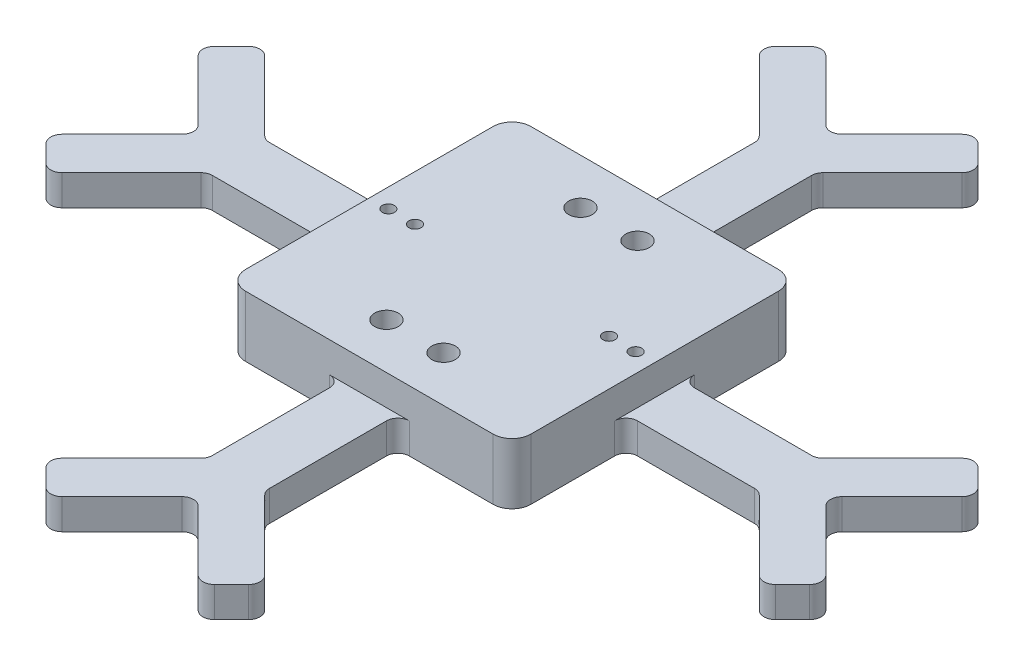
SolidWorks part; units mm, degrees
ref_plane "Front Plane" through (0, 0, 0) normal (0, 0, 1) x (1, 0, 0)
ref_plane "Top Plane" through (0, 0, 0) normal (0, 1, 0) x (1, 0, 0)
ref_plane "Right Plane" through (0, 0, 0) normal (1, 0, 0) x (0, 0, -1)
sketch "Sketch1" plane through (0, 0, 0) normal (0, 1, 0) x (1, 0, 0)
  line L0 (0, 37.5) -> (0, -37.5) construction
  line L1 (-37.5, 37.5) -> (37.5, 37.5)
  line L2 (-37.5, 37.5) -> (-37.5, -37.5)
  line L3 (-37.5, -37.5) -> (37.5, -37.5)
  line L4 (37.5, 37.5) -> (37.5, -37.5)
  line L5 (-37.5, 0) -> (37.5, 0) construction
  line L6 (-37.5, 0) -> (-20.5, 0) construction
  line L15 (-37.5, 5) -> (-20.5, 5) construction
  line L16 (-37.5, 5) -> (-37.5, -5) construction
  line L17 (-37.5, -5) -> (-20.5, -5) construction
  line L18 (-20.5, 5) -> (-20.5, -5) construction
  line L19 (-29, 5) -> (-29, -5) construction
  line L20 (29, 5) -> (29, -5) construction
  line L21 (37.5, 0) -> (20.5, 0) construction
  line L22 (20.5, 5) -> (20.5, -5) construction
  line L23 (37.5, -5) -> (20.5, -5) construction
  line L24 (37.5, 5) -> (37.5, -5) construction
  line L25 (37.5, 5) -> (20.5, 5) construction
  line L26 (-15, -25.5) -> (15, -25.5) construction
  line L27 (-15, -13.5) -> (15, -13.5) construction
  line L28 (-15, -13.5) -> (-15, -37.5) construction
  line L29 (-15, -37.5) -> (15, -37.5) construction
  line L30 (15, -13.5) -> (15, -37.5) construction
  line L31 (0, -13.5) -> (0, -37.5) construction
  line L32 (0, 13.5) -> (0, 37.5) construction
  line L33 (-15, 25.5) -> (15, 25.5) construction
  line L34 (15, 13.5) -> (15, 37.5) construction
  line L35 (-15, 37.5) -> (15, 37.5) construction
  line L36 (-15, 13.5) -> (-15, 37.5) construction
  line L37 (-15, 13.5) -> (15, 13.5) construction
  circle A2 centre (-32.5, 0) radius 1.6
  circle A3 centre (-25.5, 0) radius 1.6
  circle A4 centre (25.5, 0) radius 1.6
  circle A5 centre (32.5, 0) radius 1.6
  circle A6 centre (-7.5, -25.5) radius 3.1
  circle A7 centre (7.5, -25.5) radius 3.1
  circle A8 centre (7.5, 25.5) radius 3.1
  circle A9 centre (-7.5, 25.5) radius 3.1
  point P4 (0, 37.5)
  point P6 (-37.5, 0)
  point P19 (-29, 0)
  point P41 (29, 0)
  point P45 (0, 0)
  point P48 (0, -25.5)
  point P49 (0, 0)
  point P50 (0, 0)
  point P51 (0, 0)
  point P62 (0, 25.5)
  point P63 (45.5841, -44.9628)
  point P64 (37.328, -37.328)
  point P65 (51.459, -51.459)
  point P66 (-55.1118, 55.1118)
  dimension "D1" = 10
  dimension "D2" = 3.2
  dimension "D3" = 5
  dimension "D4" = 7
  dimension "D5" = 6.2
  dimension "D7" = 15
  dimension "D6" = 30
  dimension "D8" = 12
  dimension "D9" = 75
extrude "Boss-Extrude1" add sketch "Sketch1" along normal blind 8
sketch "Sketch3" plane through (0, 0, 0) normal (0, -1, 0) x (1, 0, 0)
  line L0 (-37.5, -37.5) -> (-37.5, 37.5) construction
  line L1 (37.5, -37.5) -> (-37.5, -37.5) construction
  line L2 (37.5, 37.5) -> (37.5, -37.5) construction
  line L3 (-37.5, 37.5) -> (37.5, 37.5) construction
  line L4 (-37.5, -37.5) -> (-37.5, 37.5)
  line L5 (37.5, -37.5) -> (-37.5, -37.5)
  line L6 (37.5, 37.5) -> (37.5, -37.5)
  line L7 (-37.5, 37.5) -> (37.5, 37.5)
  circle A0 centre (-7.5, -25.5) radius 3.1 construction
  circle A1 centre (7.5, -25.5) radius 3.1 construction
  circle A2 centre (32.5, 0) radius 1.6 construction
  circle A3 centre (25.5, 0) radius 1.6 construction
  circle A4 centre (7.5, 25.5) radius 3.1 construction
  circle A5 centre (-7.5, 25.5) radius 3.1 construction
  circle A6 centre (-25.5, 0) radius 1.6 construction
  circle A7 centre (-32.5, 0) radius 1.6 construction
  circle A8 centre (-7.5, -25.5) radius 3.1
  circle A9 centre (7.5, -25.5) radius 3.1
  circle A10 centre (32.5, 0) radius 1.6
  circle A11 centre (25.5, 0) radius 1.6
  circle A12 centre (7.5, 25.5) radius 3.1
  circle A13 centre (-7.5, 25.5) radius 3.1
  circle A14 centre (-25.5, 0) radius 1.6
  circle A15 centre (-32.5, 0) radius 1.6
extrude "Boss-Extrude2" add sketch "Sketch3" along normal blind 8
sketch "Sketch5" plane through (0, -8, 0) normal (0, -1, 0) x (1, 0, 0)
  line L0 (0, 37.5) -> (0, -37.5) construction
  line L1 (37.5, 37.5) -> (-37.5, 37.5) construction
  line L2 (-37.5, -37.5) -> (37.5, -37.5) construction
  line L3 (-37.5, 0) -> (37.5, 0) construction
  line L4 (-37.5, 37.5) -> (-37.5, -37.5) construction
  line L5 (37.5, -37.5) -> (37.5, 37.5) construction
  circle A0 centre (-7.5, -25.5) radius 5.05
  circle A1 centre (7.5, -25.5) radius 5.05
  circle A2 centre (7.5, 25.5) radius 5.05
  circle A3 centre (-7.5, 25.5) radius 5.05
  circle A4 centre (-32.5, 0) radius 2.95
  circle A5 centre (-25.5, 0) radius 2.95
  circle A6 centre (25.5, 0) radius 2.95
  circle A7 centre (32.5, 0) radius 2.95
  dimension "D1" = 10.1
  dimension "D2" = 5.9
  dimension "D3" = 5.9
extrude "Cut-Extrude1" cut sketch "Sketch5" against normal blind 6.1
ref_plane "Plane1" through (0, -8, 0) normal (0, -1, 0) x (-1, 0, 0)
sketch "Sketch8" plane through (0, -8, 0) normal (0, -1, 0) x (-1, 0, 0)
  line L8 (-7.5, -37.5) -> (7.5, -37.5)
  line L9 (0, 0) -> (-37.5, 0) construction
  line L10 (7.5, -72.5) -> (28.75, -93.75)
  line L12 (7.5, -37.5) -> (7.5, -72.5)
  line L14 (-7.5, -37.5) -> (-7.5, -72.5)
  line L15 (28.75, -93.75) -> (20, -102.5)
  line L16 (20, -102.5) -> (0, -82.5)
  line L17 (0, -82.5) -> (-20, -102.5)
  line L18 (-20, -102.5) -> (-28.75, -93.75)
  line L19 (-28.75, -93.75) -> (-7.5, -72.5)
  line L20 (-37.5, 7.5) -> (-72.5, 7.5)
  line L21 (-93.75, 28.75) -> (-72.5, 7.5)
  line L22 (-102.5, 20) -> (-93.75, 28.75)
  line L23 (-82.5, 0) -> (-102.5, 20)
  line L24 (-102.5, -20) -> (-82.5, 0)
  line L25 (-93.75, -28.75) -> (-102.5, -20)
  line L26 (-72.5, -7.5) -> (-93.75, -28.75)
  line L27 (-37.5, -7.5) -> (-72.5, -7.5)
  line L29 (7.5, 37.5) -> (7.5, 72.5)
  line L30 (28.75, 93.75) -> (7.5, 72.5)
  line L31 (20, 102.5) -> (28.75, 93.75)
  line L32 (0, 82.5) -> (20, 102.5)
  line L33 (-20, 102.5) -> (0, 82.5)
  line L34 (-28.75, 93.75) -> (-20, 102.5)
  line L35 (-7.5, 72.5) -> (-28.75, 93.75)
  line L36 (-7.5, 37.5) -> (-7.5, 72.5)
  line L38 (37.5, -7.5) -> (72.5, -7.5)
  line L39 (93.75, -28.75) -> (72.5, -7.5)
  line L40 (102.5, -20) -> (93.75, -28.75)
  line L41 (82.5, 0) -> (102.5, -20)
  line L42 (102.5, 20) -> (82.5, 0)
  line L43 (93.75, 28.75) -> (102.5, 20)
  line L44 (72.5, 7.5) -> (93.75, 28.75)
  line L45 (37.5, 7.5) -> (72.5, 7.5)
  line L47 (-37.5, 7.5) -> (-37.5, -7.5)
  line L48 (37.5, 7.5) -> (37.5, -7.5)
  line L49 (-7.5, 37.5) -> (7.5, 37.5)
  line L50 (37.5, -37.5) -> (-37.5, -37.5) construction
  point P0 (0, 0)
  dimension "D1" = 15
  dimension "D2" = 35
  dimension "D3" = 90
  dimension "D4" = 10
  dimension "D5" = 30
  dimension "D6" = 4
extrude "Boss-Extrude3" add sketch "Sketch8" against normal blind 8
fillet "Fillet1" radius 3 36 edges at (7.5, -4, -72.5) (-7.5, -4, -72.5) (28.75, -4, -93.75) (20, -4, -102.5) (0, -4, -82.5) (-20, -4, -102.5) (-28.75, -4, -93.75) (-7.5, -4, -37.5) (-37.5, -4, -7.5) (-72.5, -4, -7.5) (-93.75, -4, -28.75) (-102.5, -4, -20) (-102.5, -4, 20) (-82.5, -4, 0) (-93.75, -4, 28.75) (-72.5, -4, 7.5) (-37.5, -4, 7.5) (-7.5, -4, 37.5) (-7.5, -4, 72.5) (-28.75, -4, 93.75) (-20, -4, 102.5) (0, -4, 82.5) (20, -4, 102.5) (28.75, -4, 93.75) (7.5, -4, 72.5) (7.5, -4, 37.5) (37.5, -4, 7.5) (72.5, -4, 7.5) (93.75, -4, 28.75) (102.5, -4, 20) (82.5, -4, 0) (102.5, -4, -20) (93.75, -4, -28.75) (72.5, -4, -7.5) (7.5, -4, -37.5) (37.5, -4, -7.5)
fillet "Fillet2" radius 5 4 edges at (37.5, 0, 37.5) (37.5, 0, -37.5) (-37.5, 0, -37.5) (-37.5, 0, 37.5)
